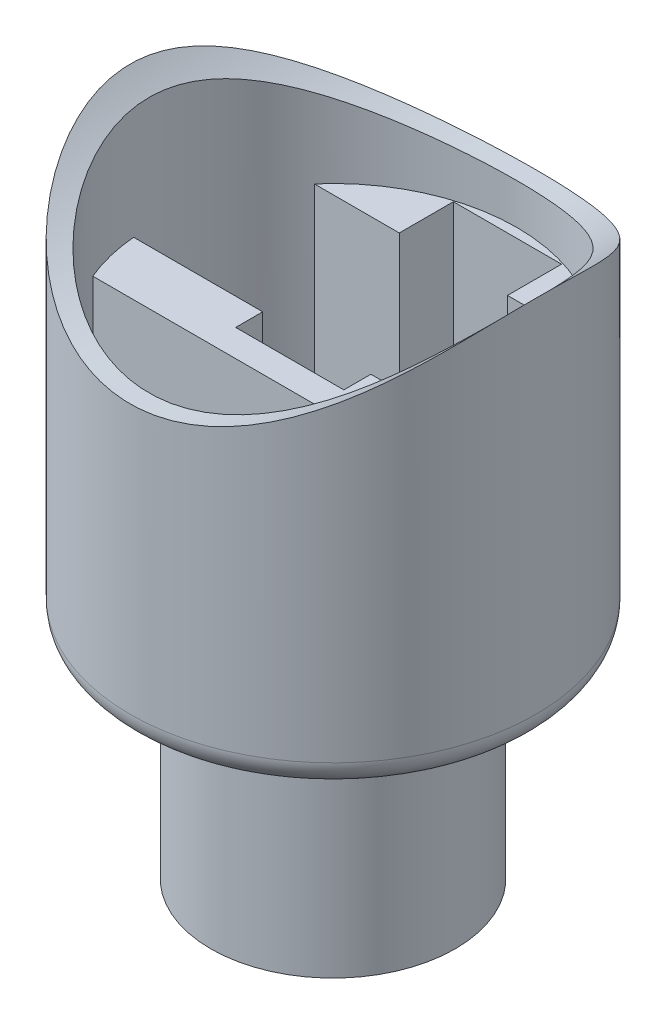
SolidWorks part; units mm, degrees
ref_plane "Front Plane" through (0, 0, 0) normal (0, 0, 1) x (1, 0, 0)
ref_plane "Top Plane" through (0, 0, 0) normal (0, 1, 0) x (1, 0, 0)
ref_plane "Right Plane" through (0, 0, 0) normal (1, 0, 0) x (0, 0, -1)
sketch "Sketch1" plane through (0, 0, 0) normal (0, 1, 0) x (1, 0, 0)
  circle A0 centre (0, 0) radius 34
  circle A1 centre (0, 0) radius 37.5
  dimension "D1" = 75
  dimension "D2" = 68
extrude "Boss-Extrude1" add sketch "Sketch1" along normal blind 10 contours A1 A0 | A0 region at (0, 0, 0) region at (-36.4393, 0, 0)
sketch "Sketch2" plane through (0, 10, 0) normal (0, 1, 0) x (1, 0, 0)
  line L0 (-25.7087, 22.25) -> (-10, 22.25)
  line L1 (-10, 32.25) -> (10, 32.25)
  line L2 (-10, 32.25) -> (-10, -8)
  line L3 (-10, -8) -> (10, -8)
  line L4 (10, 32.25) -> (10, -8)
  line L5 (-33.8674, -3) -> (-10, -3)
  line L6 (-31.4166, -13) -> (31.4166, -13)
  line L7 (0, -5.5) -> (0, 5.5) construction
  line L8 (33.8674, -3) -> (10, -3)
  line L9 (25.7087, 22.25) -> (10, 22.25)
  circle A0 centre (0, 0) radius 34
  point P16 (0, -13)
  circle M9 centre (0, 0) radius 37.5
  dimension "D1" = 68
  dimension "D2" = 40.25
  dimension "D3" = 20
  dimension "D4" = 10
  dimension "D5" = 8
  dimension "D6" = 5
  dimension "D7" = 5
  dimension "D8" = 10
extrude "Boss-Extrude2" add sketch "Sketch2" along normal blind 37.2 contours L9 A0 L0 L2 L1 L4 | L6 A0 L8 L4 L3 L2 L5 region at (0, 10, -33.4726) region at (0, 10, 8.375)
extrude "Boss-Extrude3" add sketch "Sketch2<3>" along normal blind 94.7 contours A0 M9 region at (-36.4393, 10, 0)
sketch "Sketch2<3>" plane through (0, 10, 0) normal (0, 1, 0) x (1, 0, 0) same geometry as "Sketch2"
sketch "Sketch3" plane through (0, 0, 0) normal (0, 0, 1) x (1, 0, 0)
  line L0 (37.5, 104.7) -> (-37.5, 104.7) construction
  circle A0 centre (0, 104.7) radius 50
  dimension "D1" = 100
  dimension "D2" = 0
extrude "Cut-Extrude2" cut sketch "Sketch3" against normal blind 60 and the other way blind 60 contours A0
sketch "Sketch4" plane through (0, 0, 0) normal (0, -1, 0) x (1, 0, 0)
  circle A0 centre (0, 0) radius 22.6
  circle A1 centre (0, 0) radius 19.6
  dimension "D1" = 45.2
  dimension "D2" = 3
extrude "Boss-Extrude4" add sketch "Sketch4" along normal blind 40
fillet "Fillet1" radius 5 1 edges at (0, 0, 37.5)
